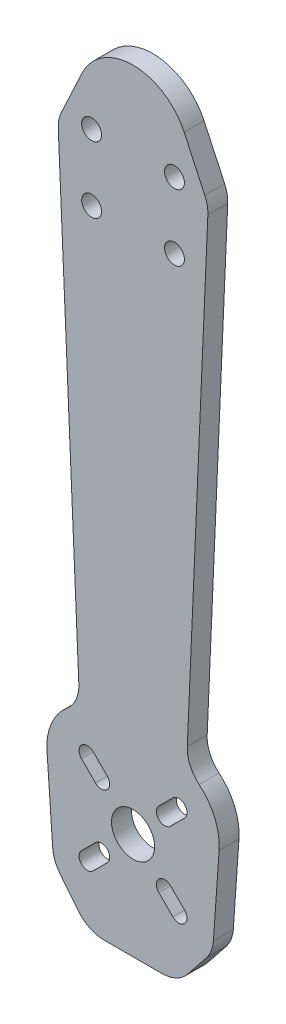
SolidWorks part; units mm, degrees
ref_plane "Front Plane" through (0, 0, 0) normal (0, 0, 1) x (1, 0, 0)
ref_plane "Top Plane" through (0, 0, 0) normal (0, 1, 0) x (1, 0, 0)
ref_plane "Right Plane" through (0, 0, 0) normal (1, 0, 0) x (0, 0, -1)
sketch "Sketch1" plane through (0, 0, 0) normal (0, 0, 1) x (1, 0, 0)
  line L0 (8.1815, 15.5604) -> (11.2824, 86.5808)
  line L1 (10.8187, 88.912) -> (7.7036, 95.5923)
  line L2 (-7.7036, 95.5923) -> (-10.8187, 88.912)
  line L3 (-11.2824, 86.5808) -> (-8.1815, 15.5604)
  line L4 (-12.9793, 4.4071) -> (-12.1223, -7.8488)
  line L5 (-11.0475, -10.6126) -> (-8.2635, -14.1126)
  line L6 (-4.3504, -16) -> (4.3504, -16)
  line L7 (8.2635, -14.1126) -> (11.0475, -10.6126)
  line L8 (12.1223, -7.8488) -> (12.9793, 4.4071)
  line L9 (7.7782, 6.0104) -> (5.6569, 3.8891)
  line L10 (3.8891, 5.6569) -> (6.0104, 7.7782)
  line L11 (-5.6569, 3.8891) -> (-7.7782, 6.0104)
  line L12 (-6.0104, 7.7782) -> (-3.8891, 5.6569)
  line L13 (-3.8891, -5.6569) -> (-6.0104, -7.7782)
  line L14 (-7.7782, -6.0104) -> (-5.6569, -3.8891)
  line L15 (6.0104, -7.7782) -> (3.8891, -5.6569)
  line L16 (5.6569, -3.8891) -> (7.7782, -6.0104)
  circle A0 centre (0, 0) radius 3.25
  arc A1 (11.2824, 86.5808) -> (10.8187, 88.912) centre (6.2871, 86.7989) ccw
  arc A2 (7.7036, 95.5923) -> (-7.7036, 95.5923) centre (0, 92) ccw
  arc A3 (-10.8187, 88.912) -> (-11.2824, 86.5808) centre (-6.2871, 86.7989) ccw
  arc A4 (-8.1815, 15.5604) -> (-9.9632, 11.5118) centre (-13.1768, 15.3423) cw
  arc A5 (-9.9632, 11.5118) -> (-12.9793, 4.4071) centre (-4.5, 5) ccw
  arc A6 (-12.1223, -7.8488) -> (-11.0475, -10.6126) centre (-7.1345, -7.5) ccw
  arc A7 (-8.2635, -14.1126) -> (-4.3504, -16) centre (-4.3504, -11) ccw
  arc A8 (4.3504, -16) -> (8.2635, -14.1126) centre (4.3504, -11) ccw
  arc A9 (11.0475, -10.6126) -> (12.1223, -7.8488) centre (7.1345, -7.5) ccw
  arc A10 (12.9793, 4.4071) -> (9.9632, 11.5118) centre (4.5, 5) ccw
  arc A11 (9.9632, 11.5118) -> (8.1815, 15.5604) centre (13.1768, 15.3423) cw
  circle A12 centre (6.25, 89) radius 1.5
  circle A13 centre (6.25, 79) radius 1.5
  circle A14 centre (-6.25, 89) radius 1.5
  circle A15 centre (-6.25, 79) radius 1.5
  arc A16 (6.0104, 7.7782) -> (7.7782, 6.0104) centre (6.8943, 6.8943) cw
  arc A17 (5.6569, 3.8891) -> (3.8891, 5.6569) centre (4.773, 4.773) cw
  arc A18 (-7.7782, 6.0104) -> (-6.0104, 7.7782) centre (-6.8943, 6.8943) cw
  arc A19 (-3.8891, 5.6569) -> (-5.6569, 3.8891) centre (-4.773, 4.773) cw
  arc A20 (-5.6569, -3.8891) -> (-3.8891, -5.6569) centre (-4.773, -4.773) cw
  arc A21 (-6.0104, -7.7782) -> (-7.7782, -6.0104) centre (-6.8943, -6.8943) cw
  arc A22 (7.7782, -6.0104) -> (6.0104, -7.7782) centre (6.8943, -6.8943) cw
  arc A23 (3.8891, -5.6569) -> (5.6569, -3.8891) centre (4.773, -4.773) cw
extrude "arm" add sketch "Sketch1" against normal blind 3
